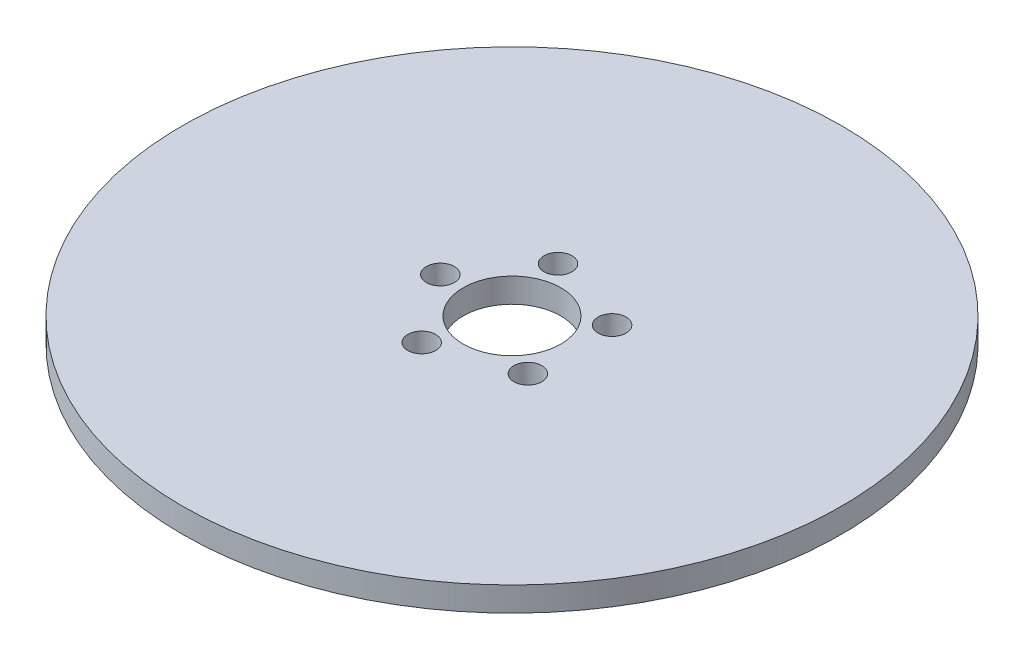
SolidWorks part; units mm, degrees
ref_plane "Front Plane" through (0, 0, 0) normal (0, 0, 1) x (1, 0, 0)
ref_plane "Top Plane" through (0, 0, 0) normal (0, 1, 0) x (1, 0, 0)
ref_plane "Right Plane" through (0, 0, 0) normal (1, 0, 0) x (0, 0, -1)
sketch "Sketch1" plane through (0, 0, 0) normal (0, 1, 0) x (1, 0, 0)
  circle A0 centre (0, 0) radius 67.5
  dimension "FLANGE_OD" = 135
extrude "Boss-Extrude1" add sketch "Sketch1" along normal blind 5
sketch "Sketch2" plane through (0, 0, 0) normal (0, 1, 0) x (1, 0, 0)
  circle A0 centre (0, 0) radius 10
  dimension "BORE_D" = 20
extrude "Cut-Extrude1" cut sketch "Sketch2" along normal through all
sketch "Sketch3" plane through (0, 5, 0) normal (0, 1, 0) x (1, 0, 0)
  circle A0 centre (0, 0) radius 14.6769 construction
  circle A1 centre (-14.6769, 0) radius 2.8615
  dimension "BOLT_D" = 5.723
  dimension "BOLT_PCD" = 29.3538
extrude "Cut-Extrude2" cut sketch "Sketch3" against normal blind 4.1248
pattern_circular "CirPattern1" count 5 over 360 about axis through (0, 0, 0) along (0, 1, 0) of "Cut-Extrude2"
